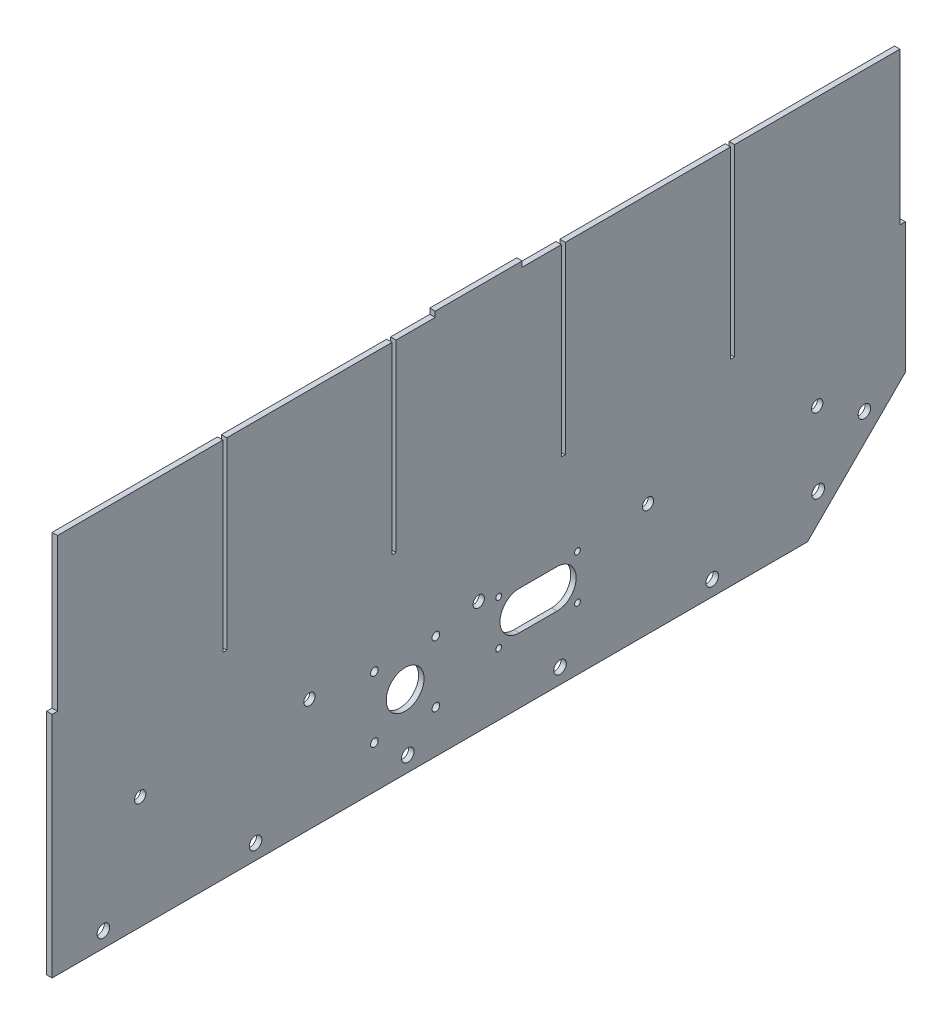
SolidWorks part; units mm, degrees
material "6061-T6 (SS)"
ref_plane "X-Y Datum" through (0, 0, 0) normal (0, 0, 1) x (1, 0, 0)
ref_plane "X-Z Datum" through (0, 0, 0) normal (0, 1, 0) x (1, 0, 0)
ref_plane "Y-Z Datum" through (0, 0, 0) normal (1, 0, 0) x (0, 0, -1)
sketch "Sketch1" plane through (0, 0, 0) normal (1, 0, 0) x (0, 0, -1)
  line L1 (-249.174, 82.55) -> (249.174, 82.55)
  line L2 (-249.174, 82.55) -> (-249.174, -82.55)
  line L3 (-249.174, -82.55) -> (249.174, -82.55)
  line L4 (249.174, 82.55) -> (249.174, -82.55)
  line L5 (-249.174, 82.55) -> (249.174, -82.55) construction
  line L6 (-249.174, -82.55) -> (249.174, 82.55) construction
  point P0 (0, 0)
  dimension "D1" = 165.1
  dimension "D2" = 498.348
extrude "Boss-Extrude1" add sketch "Sketch1" along normal mid plane 3.175
sketch "Sketch2" plane through (1.5875, 0, 0) normal (1, 0, 0) x (0, 0, -1)
  line L2 (249.174, -82.55) -> (192.024, -139.7)
  line L5 (-249.174, -82.55) -> (249.174, -82.55) construction
  line L6 (-249.174, -82.55) -> (249.174, -82.55)
  line L8 (192.024, -139.7) -> (-249.174, -139.7)
  line L9 (-249.174, -139.7) -> (-249.174, -82.55)
  line L11 (-249.174, 82.55) -> (-249.174, -82.55) construction
  line L12 (249.174, -82.55) -> (249.174, 82.55) construction
  line M10 (-249.174, -82.55) -> (249.174, -82.55)
  dimension "D1" = 45
  dimension "D5" = 57.15
extrude "Boss-Extrude2" add sketch "Sketch2" against normal blind 3.175 contours L2 M10 region at (1.5875, -110.5456, 13.9978)
sketch "Sketch3" plane through (-1.5875, 0, 0) normal (-1, 0, 0) x (0, 0, 1)
  line L0 (219.202, -139.7) -> (219.202, -130.81)
  line L1 (-192.024, -139.7) -> (249.174, -139.7) construction
  line L2 (219.202, -130.81) -> (249.174, -130.81)
  line L3 (249.174, 82.55) -> (249.174, -139.7) construction
  circle A0 centre (219.202, -130.81) radius 3.675
  dimension "D1" = 7.35
extrude "Cut-Extrude1" cut sketch "Sketch3" against normal through all contours L0 A0 L2 | L2 A0 L0 region at (-1.5875, -130.2901, 218.6821) region at (-1.5875, -132.3697, 220.7617)
pattern_linear "LPattern1" count 5 spacing 88.9 along (0, 0, -1) of "Cut-Extrude1"
sketch "Sketch4" plane through (-1.5875, 0, 0) normal (-1, 0, 0) x (0, 0, 1)
  line L0 (-206.3924, -125.3316) -> (-198.3102, -117.2494)
  line L1 (-249.174, -82.55) -> (-192.024, -139.7) construction
  line L2 (-192.024, -139.7) -> (-183.9418, -131.6178)
  line L3 (-183.9418, -131.6178) -> (-198.3102, -117.2494)
  circle A0 centre (-198.3102, -117.2494) radius 3.675
extrude "Cut-Extrude2" cut sketch "Sketch4" against normal through all and the other way through all contours L3 A0 L0 | L0 A0 L3 region at (-1.5875, -116.5141, -198.3102) region at (-1.5875, -119.4551, -198.3102)
pattern_linear "LPattern2" count 2 spacing 38.1 along (0, 0.7071, -0.7071) of "Cut-Extrude2"
sketch "Sketch5" plane through (1.5875, 0, 0) normal (1, 0, 0) x (0, 0, -1)
  line L1 (249.174, 82.55) -> (245.999, 82.55)
  line L2 (249.174, 82.55) -> (249.174, -6.35)
  line L3 (249.174, -6.35) -> (245.999, -6.35)
  line L4 (245.999, 82.55) -> (245.999, -6.35)
  line L5 (-249.174, 82.55) -> (-245.999, 82.55)
  line L6 (-249.174, 82.55) -> (-249.174, -6.35)
  line L7 (-249.174, -6.35) -> (-245.999, -6.35)
  line L8 (-245.999, 82.55) -> (-245.999, -6.35)
  dimension "D1" = 3.175
  dimension "D2" = 88.9
  dimension "D3" = 3.175
  dimension "D4" = 88.9
extrude "Cut-Extrude3" cut sketch "Sketch5" against normal through all
sketch "Sketch6" plane through (1.5875, 0, 0) normal (1, 0, 0) x (0, 0, -1)
  line L0 (122.174, 82.55) -> (249.174, 82.55) construction
  line L1 (149.4282, -24.892) -> (149.4282, 82.55) construction
  line L2 (122.174, 82.55) -> (249.174, 82.55)
  line L3 (149.4282, -24.892) -> (149.4282, 82.55)
  line L5 (149.4282, 82.55) -> (147.1422, 82.55)
  line L6 (149.4282, 82.55) -> (149.4282, -24.892)
  line L7 (149.4282, -24.892) -> (147.1422, -24.892)
  line L8 (147.1422, 82.55) -> (147.1422, -24.892)
  dimension "D1" = 2.286
  dimension "D2" = 107.442
extrude "Cut-Extrude4" cut sketch "Sketch6" against normal through all contours L2 L8 L7 L3 region at (1.5875, 28.829, -148.2852)
pattern_linear "LPattern3" count 4 spacing 98.8568 along (0, 0, 1) of "Cut-Extrude4"
sketch "Sketch8" plane through (1.5875, 0, 0) normal (1, 0, 0) x (0, 0, -1)
  line L0 (122.174, 85.725) -> (25.4, 85.725) construction
  line L1 (25.4, 82.55) -> (-25.4, 82.55)
  line L2 (25.4, 82.55) -> (25.4, 85.725)
  line L3 (25.4, 85.725) -> (-25.4, 85.725)
  line L4 (-25.4, 82.55) -> (-25.4, 85.725)
  line L5 (25.4, 82.55) -> (-25.4, 85.725) construction
  line L6 (25.4, 85.725) -> (-25.4, 82.55) construction
  point P0 (0, 84.1375)
  dimension "D1" = 3.175
  dimension "D2" = 50.8
extrude "Boss-Extrude3" add sketch "Sketch8" against normal blind 3.175
sketch "Sketch9" plane through (1.5875, 0, 0) normal (1, 0, 0) x (0, 0, -1)
  line L0 (-249.174, -6.35) -> (-249.174, -139.7) construction
  line L1 (192.024, -139.7) -> (-249.174, -139.7) construction
  circle A0 centre (-42.9768, -96.7994) radius 11.05
  dimension "D3" = 22.1
  dimension "D1" = 206.1972
  dimension "D2" = 42.9006
extrude "Cut-Extrude5" cut sketch "Sketch9" against normal through all
sketch "Sketch10" plane through (1.5875, 0, 0) normal (1, 0, 0) x (0, 0, -1)
  line L0 (192.024, -139.7) -> (-249.174, -139.7) construction
  circle A0 centre (0, -73.8124) radius 3
  dimension "D2" = 6
  dimension "D1" = 65.8876
hole_wizard "M6 Clearance Hole1" positions "Sketch11" profile "Sketch12" hole size "M6" standard "ANSI Metric" end condition through all
sketch "Sketch11" plane through (1.5875, 0, 0) normal (1, 0, 0) x (0, 0, -1)
  point P0 (0, -73.8124)
sketch "Sketch12" plane through (1.5875, -73.8124, 0) normal (0, 1, 0) x (0, 0, -1)
  line L0 (0, 0) -> (0, 3.175)
  line L1 (0, 3.175) -> (3.3, 3.175)
  line L2 (3.3, 3.175) -> (3.3, 0)
  line L5 (3.3, 0) -> (0, 0)
  line L11 (0, -6.35) -> (0, 107.95) construction
  dimension "Thru Hole Dia." = 6.6
  dimension "Thru Hole Depth" = 3.175
pattern_linear "LPattern4" count 3 spacing 98.8568 along (0, 0, 1) count 3 spacing 98.8568 along (0, 0, -1) of "M6 Clearance Hole1"
sketch "Sketch14" plane through (1.5875, 0, 0) normal (1, 0, 0) x (0, 0, -1)
  line L0 (192.024, -139.7) -> (-249.174, -139.7) construction
  line L1 (57.674, -103.315) -> (11.674, -103.315)
  line L2 (57.674, -103.315) -> (57.674, -77.315)
  line L3 (57.674, -77.315) -> (11.674, -77.315)
  line L4 (11.674, -103.315) -> (11.674, -77.315)
  line L5 (57.674, -103.315) -> (11.674, -77.315) construction
  line L6 (57.674, -77.315) -> (11.674, -103.315) construction
  line L7 (249.174, -82.55) -> (249.174, -6.35) construction
  line L8 (57.674, -90.315) -> (11.674, -90.315) construction
  line L9 (-25.0163, -114.7599) -> (-60.9373, -114.7599)
  line L10 (-25.0163, -114.7599) -> (-25.0163, -78.8389)
  line L11 (-25.0163, -78.8389) -> (-60.9373, -78.8389)
  line L12 (-60.9373, -114.7599) -> (-60.9373, -78.8389)
  line L13 (-25.0163, -114.7599) -> (-60.9373, -78.8389) construction
  line L14 (-25.0163, -78.8389) -> (-60.9373, -114.7599) construction
  line L15 (45.674, -90.315) -> (23.674, -90.315)
  line L16 (45.674, -101.565) -> (23.674, -101.565)
  line L17 (45.674, -79.065) -> (23.674, -79.065)
  arc A1 (45.674, -101.565) -> (45.674, -79.065) centre (45.674, -90.315) ccw
  arc A2 (23.674, -79.065) -> (23.674, -101.565) centre (23.674, -90.315) ccw
  point P0 (34.674, -90.315)
  point P10 (-42.9768, -96.7994)
  point P20 (34.674, -90.315)
  dimension "D7" = 11.25
  dimension "D1" = 46
  dimension "D2" = 26
  dimension "D3" = 36.385
  dimension "D4" = 191.5
  dimension "D5" = 35.921
  dimension "D6" = 22
hole_wizard "M3 Clearance Hole1" positions "Sketch15" profile "Sketch16" hole size "M3" standard "ANSI Metric" end condition through all
sketch "Sketch15" plane through (1.5875, 0, 0) normal (1, 0, 0) x (0, 0, -1)
  point P0 (11.674, -77.315)
  point P3 (11.674, -103.315)
  point P6 (57.674, -103.315)
  point P9 (57.674, -77.315)
sketch "Sketch16" plane through (1.5875, -77.315, -11.674) normal (0, 1, 0) x (0, 0, -1)
  line L0 (0, 0) -> (0, 3.175)
  line L1 (0, 3.175) -> (1.7, 3.175)
  line L2 (1.7, 3.175) -> (1.7, 0)
  line L5 (1.7, 0) -> (0, 0)
  line L11 (0, -6.35) -> (0, 107.95) construction
  dimension "Thru Hole Dia." = 3.4
  dimension "Thru Hole Depth" = 3.175
hole_wizard "M4 Clearance Hole1" positions "Sketch17" profile "Sketch18" hole size "M4" standard "ANSI Metric" end condition through all
sketch "Sketch17" plane through (1.5875, 0, 0) normal (1, 0, 0) x (0, 0, -1)
  point P0 (-25.0163, -78.8389)
  point P3 (-60.9373, -78.8389)
  point P6 (-60.9373, -114.7599)
  point P9 (-25.0163, -114.7599)
sketch "Sketch18" plane through (1.5875, -78.8389, 25.0163) normal (0, 1, 0) x (0, 0, -1)
  line L0 (0, 0) -> (0, 3.175)
  line L1 (0, 3.175) -> (2.25, 3.175)
  line L2 (2.25, 3.175) -> (2.25, 0)
  line L5 (2.25, 0) -> (0, 0)
  line L11 (0, -6.35) -> (0, 107.95) construction
  dimension "Thru Hole Dia." = 4.5
  dimension "Thru Hole Depth" = 3.175
extrude "Cut-Extrude6" cut sketch "Sketch14" against normal through all contours L17 A2 L16 A1 region at (1.5875, -101.0664, -34.674)
